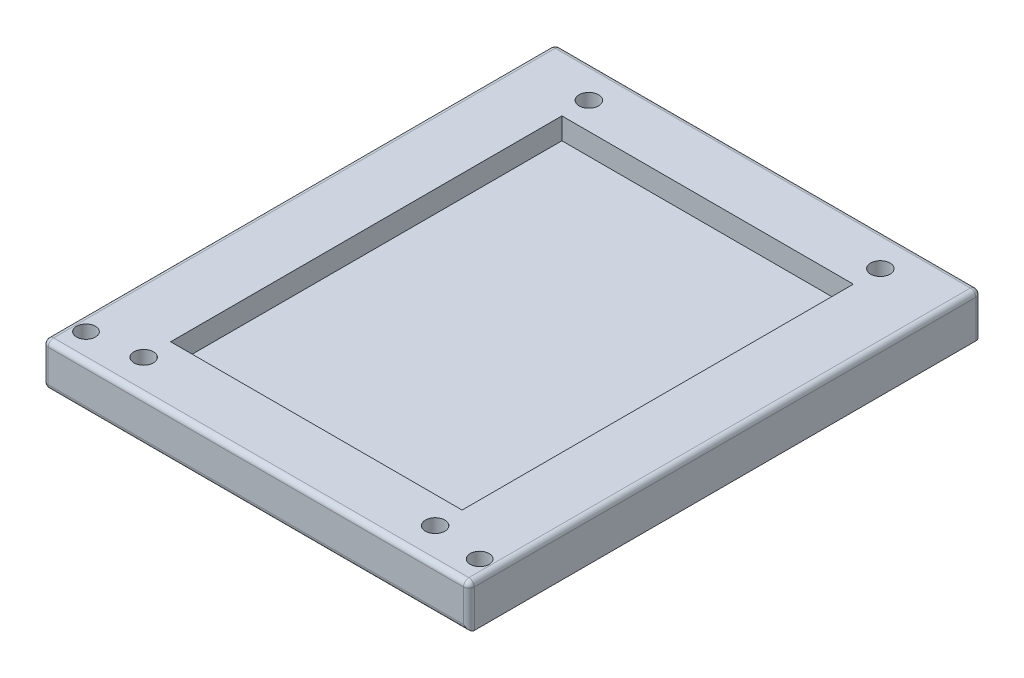
SolidWorks part; units mm, degrees
ref_plane "Front Plane" through (0, 0, 0) normal (0, 0, 1) x (1, 0, 0)
ref_plane "Top Plane" through (0, 0, 0) normal (0, 1, 0) x (1, 0, 0)
ref_plane "Right Plane" through (0, 0, 0) normal (1, 0, 0) x (0, 0, -1)
sketch "Sketch1" plane through (0, 0, 0) normal (0, 1, 0) x (1, 0, 0)
  line L0 (39.5, 95) -> (39.5, 0) construction
  line L1 (0, 0) -> (79, 0)
  line L2 (0, 0) -> (0, 95)
  line L3 (0, 95) -> (79, 95)
  line L4 (79, 0) -> (79, 95)
  circle A0 centre (3, 5) radius 1.75
  circle A1 centre (12.475, 6.225) radius 1.65 construction
  circle A2 centre (12.475, 88.775) radius 1.65 construction
  circle A3 centre (76, 5) radius 1.75
  circle A4 centre (66.525, 6.225) radius 1.65 construction
  circle A5 centre (66.525, 88.775) radius 1.65 construction
  dimension "D2" = 3
  dimension "D3" = 3.5
  dimension "D5" = 5
  dimension "D6" = 12.475
  dimension "D7" = 3.3
  dimension "D8" = 12.475
  dimension "D9" = 82.55
  dimension "D10" = 3.3
  dimension "D11" = 6.225
  dimension "D1" = 79
  dimension "D4" = 95
extrude "Boss-Extrude1" add sketch "Sketch1" along normal blind 8
sketch "Sketch3" plane through (0, 0, 0) normal (0, -1, 0) x (1, 0, 0)
  point P0 (12.475, -6.225)
  point P1 (66.525, -6.225)
  point P3 (66.525, -88.775)
  point P5 (12.475, -88.775)
hole_wizard "CBORE for M3 SHCS1" positions "Sketch3" profile "Sketch4" counterbore size "M3" standard "ANSI Metric" end condition through all
sketch "Sketch4" plane through (12.475, 0, -6.225) normal (1, 0, 0) x (0, 0, -1)
  line L0 (0, 0) -> (0, 8)
  line L1 (0, 8) -> (1.8, 8)
  line L3 (1.8, 8) -> (1.8, 3)
  line L4 (1.8, 3) -> (3.25, 3)
  line L5 (3.25, 3) -> (3.25, 0)
  line L7 (3.25, 0) -> (0, 0)
  line L11 (0, -6.35) -> (0, 107.95) construction
  dimension "Thru Hole Dia." = 3.6
  dimension "Thru Hole Depth" = 8
  dimension "C'Bore Dia." = 6.5
  dimension "C'Bore Depth" = 3
sketch "Sketch5" plane through (0, 8, 0) normal (0, 1, 0) x (1, 0, 0)
  line L1 (12.475, 83.775) -> (66.525, 83.775)
  line L2 (12.475, 83.775) -> (12.475, 11.225)
  line L3 (12.475, 11.225) -> (66.525, 11.225)
  line L4 (66.525, 83.775) -> (66.525, 11.225)
  circle A0 centre (12.475, 88.775) radius 1.65 construction
  circle A1 centre (12.475, 6.225) radius 1.65 construction
  dimension "D1" = 5
  dimension "D2" = 5
extrude "Cut-Extrude1" cut sketch "Sketch5" against normal blind 4
sketch "Sketch6" plane through (0, 0, 0) normal (0, -1, 0) x (1, 0, 0)
  line L1 (9.475, -30) -> (14.475, -30)
  line L2 (9.475, -30) -> (9.475, -50)
  line L3 (9.475, -50) -> (14.475, -50)
  line L4 (14.475, -30) -> (14.475, -50)
  dimension "D1" = 5
  dimension "D2" = 20
  dimension "D3" = 3
  dimension "D4" = 25
extrude "Boss-Extrude2" add sketch "Sketch6" along normal blind 8.8
sketch "Sketch7" plane through (0, 0, -50) normal (0, 0, -1) x (-1, 0, 0)
  line L0 (-14.475, -8.8) -> (-14.475, 0) construction
  line L1 (-9.475, 0) -> (-12.675, 0)
  line L2 (-9.475, 0) -> (-9.475, -6.8)
  line L3 (-9.475, -6.8) -> (-12.675, -6.8)
  line L4 (-12.675, 0) -> (-12.675, -6.8)
  dimension "D1" = 6.8
  dimension "D2" = 1.8
extrude "Cut-Extrude2" cut sketch "Sketch7" against normal through all
fillet "Fillet1" radius 6 1 edges at (14.475, 0, -40) second distance 8 first distance on face at (12.475, 0, -9.475)
fillet "Fillet2" radius 1 10 edges at (0, 4, 0) (39.5, 8, 0) (79, 4, 0) (79, 4, -95) (79, 8, -47.5) (39.5, 8, -95) (0, 4, -95) (0, 8, -47.5) (0, 0, -47.5) (39.5, 0, 0)
